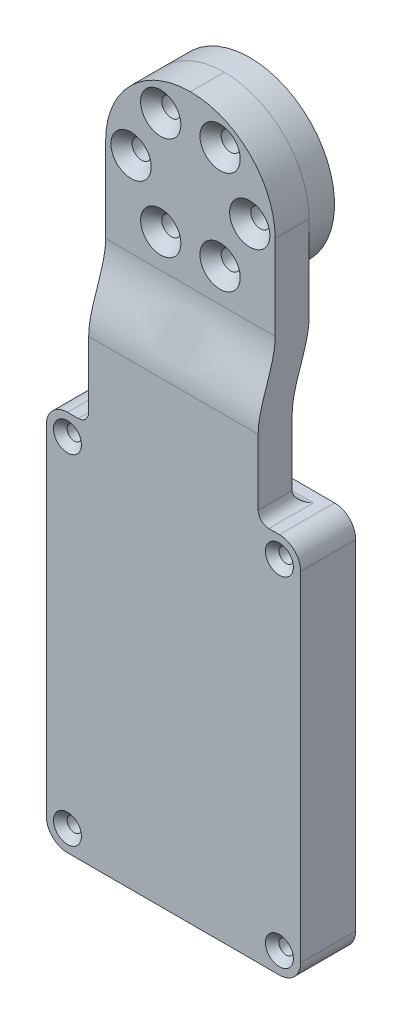
SolidWorks part; units mm, degrees
other "Markup1"
sketch "Sketch13" plane through (20, -53, 11) normal (0.0614, -0.6805, 0.7302) x (0.9699, -0.1321, -0.2046)
sketch "Sketch25" plane through (23.1, -99, 18.0001) normal (0.0614, -0.6805, 0.7302) x (0.9699, -0.1321, -0.2046)
sketch "Sketch26" plane through (23.1, -99, 18.0001) normal (0.0614, -0.6805, 0.7302) x (0.9699, -0.1321, -0.2046)
sketch "Sketch29" plane through (30, -126, 18.0001) normal (0.0614, -0.6805, 0.7302) x (0.9699, -0.1321, -0.2046)
sketch "Sketch31" plane through (30, -126, 18.0001) normal (0.0614, -0.6805, 0.7302) x (0.9699, -0.1321, -0.2046)
sketch "Sketch33" plane through (30, -136, 18.0001) normal (0.0614, -0.6805, 0.7302) x (0.9699, -0.1321, -0.2046)
other "Markup2"
sketch "Sketch30" plane through (30, 20, 18.0001) normal (0.1823, 0.1902, 0.9647) x (0.9812, 0.0279, -0.1909)
sketch "Sketch32" plane through (30, 20, 18.0001) normal (0.1823, 0.1902, 0.9647) x (0.9812, 0.0279, -0.1909)
sketch "Sketch34" plane through (30, 20, 18.0001) normal (0.1823, 0.1902, 0.9647) x (0.9812, 0.0279, -0.1909)
ref_plane "Front Plane" through (0, 0, 0) normal (0, 0, 1) x (1, 0, 0)
ref_plane "Top Plane" through (0, 0, 0) normal (0, 1, 0) x (1, 0, 0)
ref_plane "Right Plane" through (0, 0, 0) normal (1, 0, 0) x (0, 0, -1)
sketch "Sketch7" plane through (0, 0, 0) normal (0, 0, 1) x (1, 0, 0)
  line L1 (-20, 20) -> (20, 20)
  line L2 (-20, 20) -> (-20, -20)
  line L3 (-20, -20) -> (20, -20)
  line L4 (20, 20) -> (20, -20)
  line L5 (-20, 20) -> (20, -20) construction
  line L6 (-20, -20) -> (20, 20) construction
  point P0 (0, 0)
extrude "Boss-Extrude1" add sketch "Sketch7" along normal blind 14
ref_plane "Plane2" through (0, -22.1603, 5.9378) normal (0, -0.9659, 0.2588) x (1, 0, 0)
sketch "Sketch8" plane through (0, -20, 2.0782) normal (0, -1, 0) x (1, 0, 0)
  line L0 (20, 11.9218) -> (20, -2.0782) construction
  line L1 (-20, 11.9218) -> (20, 11.9218)
  line L2 (-20, 11.9218) -> (-20, 3.9218)
  line L3 (-20, 3.9218) -> (20, 3.9218)
  line L4 (20, 11.9218) -> (20, 3.9218)
  line L5 (0, 3.9218) -> (0, 11.9218) construction
  line L6 (-20, 7.9218) -> (20, 7.9218) construction
  line L7 (-20, -2.0782) -> (20, -2.0782) construction
  point P764 (0, 7.9218)
  dimension "D1" = 6
ref_plane "Plane4" through (0, -38, 0) normal (0, -1, 0) x (-1, 0, 0)
sketch "Sketch19" plane through (0, -38, 0) normal (0, -1, 0) x (-1, 0, 0)
  line L5 (20, -10) -> (-20, -10) construction
  line L6 (20, -18) -> (-20, -18)
  line L10 (20, -18) -> (20, -10)
  line L11 (20, -10) -> (-20, -10)
  line L12 (-20, -18) -> (-20, -10)
  line L13 (20, -18) -> (-20, -10) construction
  line L14 (20, -10) -> (-20, -18) construction
  line L16 (20, -14) -> (20, 0) construction
  point P0 (0, -14)
  dimension "D1" = 40
  dimension "D2" = 8
  dimension "D3" = 4
loft "Loft1" add profiles "Sketch19", "Sketch8<3>" start constraint normal to profile start tangent length 1 end constraint normal to profile end tangent length 1 connector at (-20, -38, 18) connector at (-20, -20, 14)
sketch "Sketch8<3>" plane through (0, -20, 2.0782) normal (0, -1, 0) x (1, 0, 0) same geometry as "Sketch8"
sketch "Sketch16" plane through (0, 0, 0) normal (0, 0, -1) x (-1, 0, 0)
  line L1 (24.5131, 32.6211) -> (-24.5131, 32.6211)
  line L2 (24.5131, 32.6211) -> (24.5131, -32.6211)
  line L3 (24.5131, -32.6211) -> (-24.5131, -32.6211)
  line L4 (-24.5131, 32.6211) -> (-24.5131, -32.6211)
  line L5 (24.5131, 32.6211) -> (-24.5131, -32.6211) construction
  line L6 (24.5131, -32.6211) -> (-24.5131, 32.6211) construction
  circle A0 centre (0, 0) radius 20
extrude "Cut-Extrude3" cut sketch "Sketch16" against normal blind 6
ref_plane "Plane3" [suppressed] through (0, -56, 0) normal (0, -1, 0) x (-1, 0, 0)
sketch "Sketch17" plane through (0, -38, 0) normal (0, -1, 0) x (-1, 0, 0)
  line L1 (20, -18) -> (-20, -18)
  line L2 (20, -18) -> (20, -10)
  line L3 (20, -10) -> (-20, -10)
  line L4 (-20, -18) -> (-20, -10)
  line L5 (20, -18) -> (-20, -10) construction
  line L6 (20, -10) -> (-20, -18) construction
  line L7 (-20, -18) -> (20, -18) construction
  line L11 (-20, -6) -> (-20, -10) construction
  line L12 (20, -14) -> (20, -6) construction
  point P4 (0, -14)
  dimension "D1" = 8
extrude "Boss-Extrude5" add sketch "Sketch17" along normal blind 18
sketch "Sketch10" plane through (0, 0, 14) normal (0, 0, 1) x (1, 0, 0)
  circle A0 centre (-7.0001, 12.1244) radius 2.25
  circle A1 centre (6.9999, 12.1244) radius 2.25
  circle A2 centre (13.9999, 0.0001) radius 2.25
  circle A3 centre (6.9999, -12.1243) radius 2.25
  circle A4 centre (-7.0001, -12.1243) radius 2.25
  circle A5 centre (-14.0001, 0.0001) radius 2.25
  point P0 (0, 0)
  point P1 (0.0025, 0.0011)
  dimension "D4" = 4.5
extrude "Cut-Extrude1" cut sketch "Sketch10" against normal blind 25
sketch "Sketch11" plane through (0, -56, -3.473) normal (0, 1, 0) x (1, 0, 0)
  line L0 (20, -21.473) -> (-20, -21.473) construction
  line L5 (30, -3.473) -> (-30, -3.473)
  line L6 (30, -3.473) -> (30, -21.473)
  line L7 (30, -21.473) -> (-30, -21.473)
  line L8 (-30, -3.473) -> (-30, -21.473)
  line L9 (30, -3.473) -> (-30, -21.473) construction
  line L10 (30, -21.473) -> (-30, -3.473) construction
  line L11 (-20, -13.473) -> (20, -13.473) construction
  point P0 (0, -12.473)
  point P9 (0, -13.473)
  dimension "D1" = 60
  dimension "D2" = 30
  dimension "D3" = 18
chamfer "Chamfer1" distance 2.5 angle 45 6 edges at (-4.7501, 12.1244, 14) (-11.7501, 0.0001, 14) (-4.7501, -12.1243, 14) (9.2499, 12.1244, 14) (16.2499, 0.0001, 14) (9.2499, -12.1243, 14)
fillet "Fillet3" radius 20 2 edges at (20, 20, 10) (-20, 20, 10)
extrude "Boss-Extrude6" add sketch "Sketch11" against normal blind 90
fillet "Fillet9" radius 2.5 3 edges at (0, -56, 10) (-20, -56, 14) (20, -56, 14)
ref_plane "Plane5" through (0, -146, 0) normal (0, -1, 0) x (-1, 0, 0)
sketch "Sketch20" plane through (0, -146, 0) normal (0, -1, 0) x (1, 0, 0)
  line L0 (0, 0) -> (0, 18) construction
  line L1 (25, 5) -> (-25, 5)
  line L2 (25, 5) -> (25, 13)
  line L3 (25, 13) -> (-25, 13)
  line L4 (-25, 5) -> (-25, 13)
  line L5 (25, 5) -> (-25, 13) construction
  line L6 (25, 13) -> (-25, 5) construction
  line L7 (30, 0) -> (-30, 0) construction
  line L8 (-30, 18) -> (30, 18) construction
  line L9 (-30, 0) -> (-30, 18) construction
  point P0 (0, 9)
  dimension "D1" = 8
  dimension "D2" = 50
  dimension "D3" = 30
  dimension "D4" = 9
extrude "Cut-Extrude4" cut sketch "Sketch20" against normal blind 80
ref_plane "Plane6" through (0, -146, 0) normal (0, -1, 0) x (-1, 0, 0)
sketch "Sketch28" plane through (0, -146, 0) normal (0, -1, 0) x (-1, 0, 0)
  line L0 (25, -5) -> (-25, -5) construction
  line L1 (25, -13) -> (10, -13)
  line L2 (25, -13) -> (25, -5)
  line L3 (25, -5) -> (10, -5)
  line L4 (10, -13) -> (10, -5)
  line L5 (-25, -13) -> (25, -13) construction
  line L6 (-25, -5) -> (-10, -5)
  line L7 (-25, -5) -> (-25, -13)
  line L8 (-25, -13) -> (-10, -13)
  line L9 (-10, -5) -> (-10, -13)
  line L10 (-25, -5) -> (-10, -13) construction
  line L11 (-25, -13) -> (-10, -5) construction
  line L12 (-25, -5) -> (-25, -13) construction
  point P7 (-17.5, -9)
  dimension "D1" = 15
  dimension "D2" = 15
extrude "Boss-Extrude7" add sketch "Sketch28" against normal blind 10
fillet "Fillet13" radius 4 6 edges at (10, -136, 9) (-10, -136, 9) (-25, -136, 9) (25, -136, 9) (25, -66, 9) (-25, -66, 9)
sketch "Sketch37" plane through (0, 0, 0) normal (0, 0, 1) x (1, 0, 0)
  line L0 (-30, -146) -> (-30, -56) construction
  line L1 (30, -56) -> (-30, -56)
  line L2 (30, -56) -> (30, -146)
  line L3 (30, -146) -> (-30, -146)
  line L4 (-30, -56) -> (-30, -146)
extrude "Cut-Extrude8" cut sketch "Sketch37" along normal blind 5
fillet "Fillet16" radius 5 4 edges at (30, -56, 11.5) (30, -146, 11.5) (-30, -146, 11.5) (-30, -56, 11.5)
sketch "Sketch38" plane through (0, 0, 0) normal (0, 0, 1) x (1, 0, 0)
  circle A1 centre (25, -61) radius 1.7
  circle A2 centre (-25, -61) radius 1.7
  circle A3 centre (-25, -141) radius 1.7
  circle A4 centre (25, -141) radius 1.7
  dimension "D1" = 3.4
extrude "Cut-Extrude9" cut sketch "Sketch38" along normal blind 22
chamfer "Chamfer3" distance 1.6 angle 45 4 edges at (23.3, -61, 18) (-26.7, -61, 18) (-26.7, -141, 18) (23.3, -141, 18)
